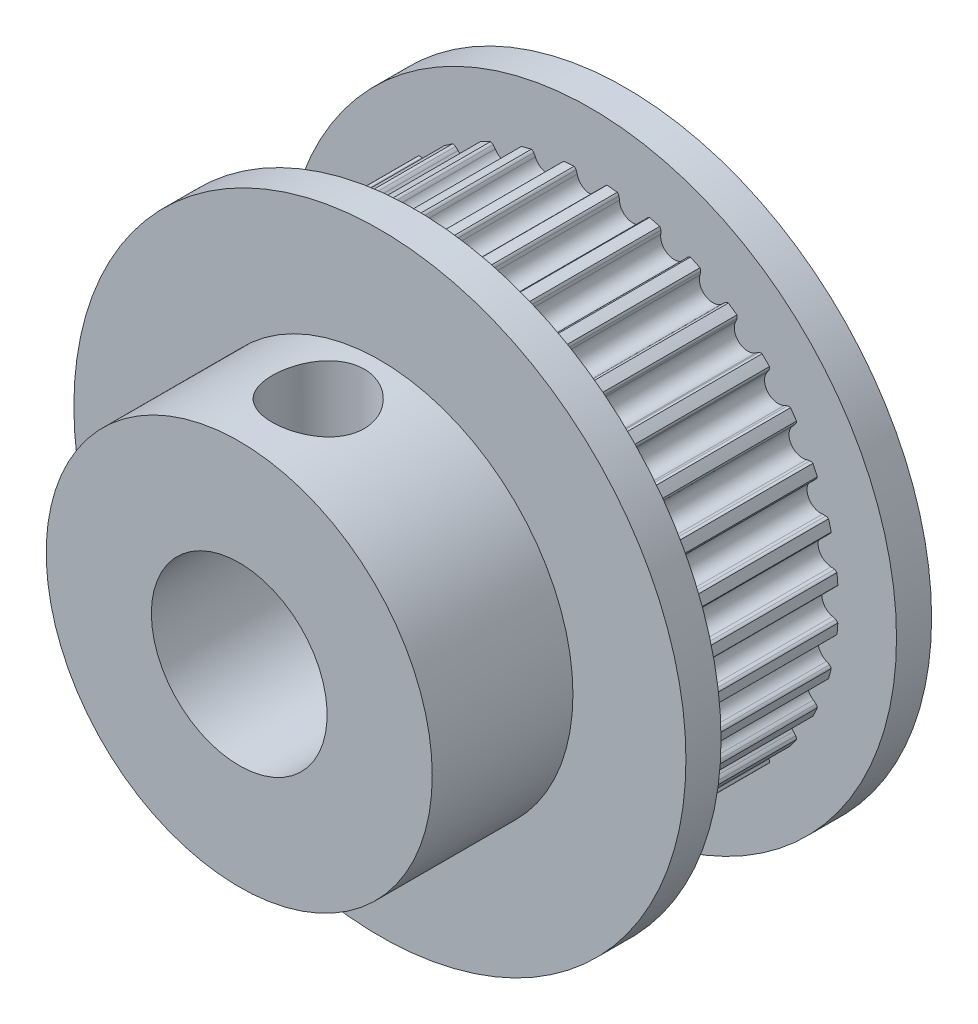
SolidWorks part; units mm, degrees
ref_plane "Front Plane" through (0, 0, 0) normal (0, 0, 1) x (1, 0, 0)
ref_plane "Top Plane" through (0, 0, 0) normal (0, 1, 0) x (1, 0, 0)
ref_plane "Right Plane" through (0, 0, 0) normal (1, 0, 0) x (0, 0, -1)
sketch "Sketch1" plane through (0, 0, 0) normal (0, 1, 0) x (1, 0, 0)
  line L0 (13.843, -3.9687) -> (0, -3.9687)
  line L1 (0, -3.9687) -> (0, -5.5562)
  line L2 (0, -5.5562) -> (13.843, -5.5562)
  line L3 (13.843, -5.5562) -> (13.843, -3.9687)
  line L4 (0, -3.9687) -> (0, -5.5562) construction
revolve "Revolve1" add sketch "Sketch1" angle 360 about L4 reverse direction yes
sketch "Sketch2" plane through (0, 0, 3.9687) normal (0, 0, -1) x (-1, 0, 0)
  arc A0 (-3.1309, 10.7682) -> (-2.6727, 10.891) centre (0, 0) cw
  arc A6 (-1.2134, 11.1483) -> (-0.7409, 11.1896) centre (0, 0) cw
  arc A7 (-4.5233, 10.2614) -> (-4.4045, 10.2) centre (-4.5654, 10.0341) cw
  arc A8 (-4.4045, 10.2) -> (-4.3083, 10.0819) centre (-4.8573, 9.7334) cw
  arc A9 (-4.3083, 10.0819) -> (-3.1801, 10.4925) centre (-3.7894, 10.4113) ccw
  arc A10 (-3.1801, 10.4925) -> (-3.1824, 10.6448) centre (-2.5356, 10.5784) cw
  arc A11 (-3.1824, 10.6448) -> (-3.1309, 10.7682) centre (-2.9525, 10.6212) cw
  arc A12 (-2.6727, 10.891) -> (-2.5663, 10.8099) centre (-2.7537, 10.6745) cw
  arc A13 (-2.5663, 10.8099) -> (-2.4922, 10.6768) centre (-3.0933, 10.429) cw
  arc A14 (-2.4922, 10.6768) -> (-1.3098, 10.8853) centre (-1.9239, 10.9112) ccw
  arc A15 (-1.3098, 10.8853) -> (-1.2856, 11.0357) centre (-0.6601, 10.858) cw
  arc A16 (-1.2856, 11.0357) -> (-1.2134, 11.1483) centre (-1.0633, 10.9725) cw
  arc A17 (-0.7409, 11.1896) -> (-0.6502, 11.0913) centre (-0.8582, 10.9905) cw
  arc A18 (-0.6502, 11.0913) -> (-0.6003, 10.9474) centre (-1.2354, 10.8077) cw
  arc A19 (-0.6003, 10.9474) -> (0.6003, 10.9474) centre (0, 11.0795) ccw
  arc A20 (0.6003, 10.9474) -> (0.6502, 11.0913) centre (1.2354, 10.8077) cw
  arc A21 (0.6502, 11.0913) -> (0.7409, 11.1896) centre (0.8582, 10.9905) cw
  arc A22 (1.2134, 11.1483) -> (1.2856, 11.0357) centre (1.0633, 10.9725) cw
  arc A23 (1.2856, 11.0357) -> (1.3098, 10.8853) centre (0.6601, 10.858) cw
  arc A24 (1.3098, 10.8853) -> (2.4922, 10.6768) centre (1.9239, 10.9112) ccw
  arc A25 (2.4922, 10.6768) -> (2.5663, 10.8099) centre (3.0933, 10.429) cw
  arc A26 (2.5663, 10.8099) -> (2.6727, 10.891) centre (2.7537, 10.6745) cw
  arc A27 (3.1309, 10.7682) -> (3.1824, 10.6448) centre (2.9525, 10.6212) cw
  arc A28 (3.1824, 10.6448) -> (3.1801, 10.4925) centre (2.5356, 10.5784) cw
  arc A29 (3.1801, 10.4925) -> (4.3083, 10.0819) centre (3.7894, 10.4113) ccw
  arc A30 (4.3083, 10.0819) -> (4.4045, 10.2) centre (4.8573, 9.7334) cw
  arc A31 (4.4045, 10.2) -> (4.5233, 10.2614) centre (4.5654, 10.0341) cw
  arc A32 (4.9532, 10.0609) -> (4.9825, 9.9305) centre (4.752, 9.9471) cw
  arc A33 (4.9825, 9.9305) -> (4.9538, 9.7809) centre (4.334, 9.9774) cw
  arc A34 (4.9538, 9.7809) -> (5.9936, 9.1806) centre (5.5397, 9.5951) ccw
  arc A35 (5.9936, 9.1806) -> (6.1088, 9.2802) centre (6.4737, 8.742) cw
  arc A36 (6.1088, 9.2802) -> (6.2364, 9.32) centre (6.2385, 9.0889) cw
  arc A37 (6.625, 9.048) -> (6.6312, 8.9144) centre (6.4071, 8.9709) cw
  arc A38 (6.6312, 8.9144) -> (6.577, 8.7721) centre (6.0007, 9.0732) cw
  arc A39 (6.577, 8.7721) -> (7.4967, 8.0003) centre (7.1218, 8.4874) ccw
  arc A40 (7.4967, 8.0003) -> (7.6275, 8.0784) centre (7.8934, 7.4851) cw
  arc A41 (7.6275, 8.0784) -> (7.7601, 8.0955) centre (7.722, 7.8675) cw
  arc A42 (8.0955, 7.7601) -> (8.0784, 7.6275) centre (7.8675, 7.722) cw
  arc A43 (8.0784, 7.6275) -> (8.0003, 7.4967) centre (7.4851, 7.8934) cw
  arc A44 (8.0003, 7.4967) -> (8.7721, 6.577) centre (8.4874, 7.1218) ccw
  arc A45 (8.7721, 6.577) -> (8.9144, 6.6312) centre (9.0732, 6.0007) cw
  arc A46 (8.9144, 6.6312) -> (9.048, 6.625) centre (8.9709, 6.4071) cw
  arc A47 (9.32, 6.2364) -> (9.2802, 6.1088) centre (9.0889, 6.2385) cw
  arc A48 (9.2802, 6.1088) -> (9.1806, 5.9936) centre (8.742, 6.4737) cw
  arc A49 (9.1806, 5.9936) -> (9.7809, 4.9538) centre (9.5951, 5.5397) ccw
  arc A50 (9.7809, 4.9538) -> (9.9305, 4.9825) centre (9.9774, 4.334) cw
  arc A51 (9.9305, 4.9825) -> (10.0609, 4.9532) centre (9.9471, 4.752) cw
  arc A52 (10.2614, 4.5233) -> (10.2, 4.4045) centre (10.0341, 4.5654) cw
  arc A53 (10.2, 4.4045) -> (10.0819, 4.3083) centre (9.7334, 4.8573) cw
  arc A54 (10.0819, 4.3083) -> (10.4925, 3.1801) centre (10.4113, 3.7894) ccw
  arc A55 (10.4925, 3.1801) -> (10.6448, 3.1824) centre (10.5784, 2.5356) cw
  arc A56 (10.6448, 3.1824) -> (10.7682, 3.1309) centre (10.6212, 2.9525) cw
  arc A57 (10.891, 2.6727) -> (10.8099, 2.5663) centre (10.6745, 2.7537) cw
  arc A58 (10.8099, 2.5663) -> (10.6768, 2.4922) centre (10.429, 3.0933) cw
  arc A59 (10.6768, 2.4922) -> (10.8853, 1.3098) centre (10.9112, 1.9239) ccw
  arc A60 (10.8853, 1.3098) -> (11.0357, 1.2856) centre (10.858, 0.6601) cw
  arc A61 (11.0357, 1.2856) -> (11.1483, 1.2134) centre (10.9725, 1.0633) cw
  arc A62 (11.1896, 0.7409) -> (11.0913, 0.6502) centre (10.9905, 0.8582) cw
  arc A63 (11.0913, 0.6502) -> (10.9474, 0.6003) centre (10.8077, 1.2354) cw
  arc A64 (10.9474, 0.6003) -> (10.9474, -0.6003) centre (11.0795, 0) ccw
  arc A65 (10.9474, -0.6003) -> (11.0913, -0.6502) centre (10.8077, -1.2354) cw
  arc A66 (11.0913, -0.6502) -> (11.1896, -0.7409) centre (10.9905, -0.8582) cw
  arc A67 (11.1483, -1.2134) -> (11.0357, -1.2856) centre (10.9725, -1.0633) cw
  arc A68 (11.0357, -1.2856) -> (10.8853, -1.3098) centre (10.858, -0.6601) cw
  arc A69 (10.8853, -1.3098) -> (10.6768, -2.4922) centre (10.9112, -1.9239) ccw
  arc A70 (10.6768, -2.4922) -> (10.8099, -2.5663) centre (10.429, -3.0933) cw
  arc A71 (10.8099, -2.5663) -> (10.891, -2.6727) centre (10.6745, -2.7537) cw
  arc A72 (10.7682, -3.1309) -> (10.6448, -3.1824) centre (10.6212, -2.9525) cw
  arc A73 (10.6448, -3.1824) -> (10.4925, -3.1801) centre (10.5784, -2.5356) cw
  arc A74 (10.4925, -3.1801) -> (10.0819, -4.3083) centre (10.4113, -3.7894) ccw
  arc A75 (10.0819, -4.3083) -> (10.2, -4.4045) centre (9.7334, -4.8573) cw
  arc A76 (10.2, -4.4045) -> (10.2614, -4.5233) centre (10.0341, -4.5654) cw
  arc A77 (10.0609, -4.9532) -> (9.9305, -4.9825) centre (9.9471, -4.752) cw
  arc A78 (9.9305, -4.9825) -> (9.7809, -4.9538) centre (9.9774, -4.334) cw
  arc A79 (9.7809, -4.9538) -> (9.1806, -5.9936) centre (9.5951, -5.5397) ccw
  arc A80 (9.1806, -5.9936) -> (9.2802, -6.1088) centre (8.742, -6.4737) cw
  arc A81 (9.2802, -6.1088) -> (9.32, -6.2364) centre (9.0889, -6.2385) cw
  arc A82 (9.048, -6.625) -> (8.9144, -6.6312) centre (8.9709, -6.4071) cw
  arc A83 (8.9144, -6.6312) -> (8.7721, -6.577) centre (9.0732, -6.0007) cw
  arc A84 (8.7721, -6.577) -> (8.0003, -7.4967) centre (8.4874, -7.1218) ccw
  arc A85 (8.0003, -7.4967) -> (8.0784, -7.6275) centre (7.4851, -7.8934) cw
  arc A86 (8.0784, -7.6275) -> (8.0955, -7.7601) centre (7.8675, -7.722) cw
  arc A87 (7.7601, -8.0955) -> (7.6275, -8.0784) centre (7.722, -7.8675) cw
  arc A88 (7.6275, -8.0784) -> (7.4967, -8.0003) centre (7.8934, -7.4851) cw
  arc A89 (7.4967, -8.0003) -> (6.577, -8.7721) centre (7.1218, -8.4874) ccw
  arc A90 (6.577, -8.7721) -> (6.6312, -8.9144) centre (6.0007, -9.0732) cw
  arc A91 (6.6312, -8.9144) -> (6.625, -9.048) centre (6.4071, -8.9709) cw
  arc A92 (6.2364, -9.32) -> (6.1088, -9.2802) centre (6.2385, -9.0889) cw
  arc A93 (6.1088, -9.2802) -> (5.9936, -9.1806) centre (6.4737, -8.742) cw
  arc A94 (5.9936, -9.1806) -> (4.9538, -9.7809) centre (5.5397, -9.5951) ccw
  arc A95 (4.9538, -9.7809) -> (4.9825, -9.9305) centre (4.334, -9.9774) cw
  arc A96 (4.9825, -9.9305) -> (4.9532, -10.0609) centre (4.752, -9.9471) cw
  arc A97 (4.5233, -10.2614) -> (4.4045, -10.2) centre (4.5654, -10.0341) cw
  arc A98 (4.4045, -10.2) -> (4.3083, -10.0819) centre (4.8573, -9.7334) cw
  arc A99 (4.3083, -10.0819) -> (3.1801, -10.4925) centre (3.7894, -10.4113) ccw
  arc A100 (3.1801, -10.4925) -> (3.1824, -10.6448) centre (2.5356, -10.5784) cw
  arc A101 (3.1824, -10.6448) -> (3.1309, -10.7682) centre (2.9525, -10.6212) cw
  arc A102 (2.6727, -10.891) -> (2.5663, -10.8099) centre (2.7537, -10.6745) cw
  arc A103 (2.5663, -10.8099) -> (2.4922, -10.6768) centre (3.0933, -10.429) cw
  arc A104 (2.4922, -10.6768) -> (1.3098, -10.8853) centre (1.9239, -10.9112) ccw
  arc A105 (1.3098, -10.8853) -> (1.2856, -11.0357) centre (0.6601, -10.858) cw
  arc A106 (1.2856, -11.0357) -> (1.2134, -11.1483) centre (1.0633, -10.9725) cw
  arc A107 (0.7409, -11.1896) -> (0.6502, -11.0913) centre (0.8582, -10.9905) cw
  arc A108 (0.6502, -11.0913) -> (0.6003, -10.9474) centre (1.2354, -10.8077) cw
  arc A109 (0.6003, -10.9474) -> (-0.6003, -10.9474) centre (0, -11.0795) ccw
  arc A110 (-0.6003, -10.9474) -> (-0.6502, -11.0913) centre (-1.2354, -10.8077) cw
  arc A111 (-0.6502, -11.0913) -> (-0.7409, -11.1896) centre (-0.8582, -10.9905) cw
  arc A112 (-1.2134, -11.1483) -> (-1.2856, -11.0357) centre (-1.0633, -10.9725) cw
  arc A113 (-1.2856, -11.0357) -> (-1.3098, -10.8853) centre (-0.6601, -10.858) cw
  arc A114 (-1.3098, -10.8853) -> (-2.4922, -10.6768) centre (-1.9239, -10.9112) ccw
  arc A115 (-2.4922, -10.6768) -> (-2.5663, -10.8099) centre (-3.0933, -10.429) cw
  arc A116 (-2.5663, -10.8099) -> (-2.6727, -10.891) centre (-2.7537, -10.6745) cw
  arc A117 (-3.1309, -10.7682) -> (-3.1824, -10.6448) centre (-2.9525, -10.6212) cw
  arc A118 (-3.1824, -10.6448) -> (-3.1801, -10.4925) centre (-2.5356, -10.5784) cw
  arc A119 (-3.1801, -10.4925) -> (-4.3083, -10.0819) centre (-3.7894, -10.4113) ccw
  arc A120 (-4.3083, -10.0819) -> (-4.4045, -10.2) centre (-4.8573, -9.7334) cw
  arc A121 (-4.4045, -10.2) -> (-4.5233, -10.2614) centre (-4.5654, -10.0341) cw
  arc A122 (-4.9532, -10.0609) -> (-4.9825, -9.9305) centre (-4.752, -9.9471) cw
  arc A123 (-4.9825, -9.9305) -> (-4.9538, -9.7809) centre (-4.334, -9.9774) cw
  arc A124 (-4.9538, -9.7809) -> (-5.9936, -9.1806) centre (-5.5397, -9.5951) ccw
  arc A125 (-5.9936, -9.1806) -> (-6.1088, -9.2802) centre (-6.4737, -8.742) cw
  arc A126 (-6.1088, -9.2802) -> (-6.2364, -9.32) centre (-6.2385, -9.0889) cw
  arc A127 (-6.625, -9.048) -> (-6.6312, -8.9144) centre (-6.4071, -8.9709) cw
  arc A128 (-6.6312, -8.9144) -> (-6.577, -8.7721) centre (-6.0007, -9.0732) cw
  arc A129 (-6.577, -8.7721) -> (-7.4967, -8.0003) centre (-7.1218, -8.4874) ccw
  arc A130 (-7.4967, -8.0003) -> (-7.6275, -8.0784) centre (-7.8934, -7.4851) cw
  arc A131 (-7.6275, -8.0784) -> (-7.7601, -8.0955) centre (-7.722, -7.8675) cw
  arc A132 (-8.0955, -7.7601) -> (-8.0784, -7.6275) centre (-7.8675, -7.722) cw
  arc A133 (-8.0784, -7.6275) -> (-8.0003, -7.4967) centre (-7.4851, -7.8934) cw
  arc A134 (-8.0003, -7.4967) -> (-8.7721, -6.577) centre (-8.4874, -7.1218) ccw
  arc A135 (-8.7721, -6.577) -> (-8.9144, -6.6312) centre (-9.0732, -6.0007) cw
  arc A136 (-8.9144, -6.6312) -> (-9.048, -6.625) centre (-8.9709, -6.4071) cw
  arc A137 (-9.32, -6.2364) -> (-9.2802, -6.1088) centre (-9.0889, -6.2385) cw
  arc A138 (-9.2802, -6.1088) -> (-9.1806, -5.9936) centre (-8.742, -6.4737) cw
  arc A139 (-9.1806, -5.9936) -> (-9.7809, -4.9538) centre (-9.5951, -5.5397) ccw
  arc A140 (-9.7809, -4.9538) -> (-9.9305, -4.9825) centre (-9.9774, -4.334) cw
  arc A141 (-9.9305, -4.9825) -> (-10.0609, -4.9532) centre (-9.9471, -4.752) cw
  arc A142 (-10.2614, -4.5233) -> (-10.2, -4.4045) centre (-10.0341, -4.5654) cw
  arc A143 (-10.2, -4.4045) -> (-10.0819, -4.3083) centre (-9.7334, -4.8573) cw
  arc A144 (-10.0819, -4.3083) -> (-10.4925, -3.1801) centre (-10.4113, -3.7894) ccw
  arc A145 (-10.4925, -3.1801) -> (-10.6448, -3.1824) centre (-10.5784, -2.5356) cw
  arc A146 (-10.6448, -3.1824) -> (-10.7682, -3.1309) centre (-10.6212, -2.9525) cw
  arc A147 (-10.891, -2.6727) -> (-10.8099, -2.5663) centre (-10.6745, -2.7537) cw
  arc A148 (-10.8099, -2.5663) -> (-10.6768, -2.4922) centre (-10.429, -3.0933) cw
  arc A149 (-10.6768, -2.4922) -> (-10.8853, -1.3098) centre (-10.9112, -1.9239) ccw
  arc A150 (-10.8853, -1.3098) -> (-11.0357, -1.2856) centre (-10.858, -0.6601) cw
  arc A151 (-11.0357, -1.2856) -> (-11.1483, -1.2134) centre (-10.9725, -1.0633) cw
  arc A152 (-11.1896, -0.7409) -> (-11.0913, -0.6502) centre (-10.9905, -0.8582) cw
  arc A153 (-11.0913, -0.6502) -> (-10.9474, -0.6003) centre (-10.8077, -1.2354) cw
  arc A154 (-10.9474, -0.6003) -> (-10.9474, 0.6003) centre (-11.0795, 0) ccw
  arc A155 (-10.9474, 0.6003) -> (-11.0913, 0.6502) centre (-10.8077, 1.2354) cw
  arc A156 (-11.0913, 0.6502) -> (-11.1896, 0.7409) centre (-10.9905, 0.8582) cw
  arc A157 (-11.1483, 1.2134) -> (-11.0357, 1.2856) centre (-10.9725, 1.0633) cw
  arc A158 (-11.0357, 1.2856) -> (-10.8853, 1.3098) centre (-10.858, 0.6601) cw
  arc A159 (-10.8853, 1.3098) -> (-10.6768, 2.4922) centre (-10.9112, 1.9239) ccw
  arc A160 (-10.6768, 2.4922) -> (-10.8099, 2.5663) centre (-10.429, 3.0933) cw
  arc A161 (-10.8099, 2.5663) -> (-10.891, 2.6727) centre (-10.6745, 2.7537) cw
  arc A162 (-10.7682, 3.1309) -> (-10.6448, 3.1824) centre (-10.6212, 2.9525) cw
  arc A163 (-10.6448, 3.1824) -> (-10.4925, 3.1801) centre (-10.5784, 2.5356) cw
  arc A164 (-10.4925, 3.1801) -> (-10.0819, 4.3083) centre (-10.4113, 3.7894) ccw
  arc A165 (-10.0819, 4.3083) -> (-10.2, 4.4045) centre (-9.7334, 4.8573) cw
  arc A166 (-10.2, 4.4045) -> (-10.2614, 4.5233) centre (-10.0341, 4.5654) cw
  arc A167 (-10.0609, 4.9532) -> (-9.9305, 4.9825) centre (-9.9471, 4.752) cw
  arc A168 (-9.9305, 4.9825) -> (-9.7809, 4.9538) centre (-9.9774, 4.334) cw
  arc A169 (-9.7809, 4.9538) -> (-9.1806, 5.9936) centre (-9.5951, 5.5397) ccw
  arc A170 (-9.1806, 5.9936) -> (-9.2802, 6.1088) centre (-8.742, 6.4737) cw
  arc A171 (-9.2802, 6.1088) -> (-9.32, 6.2364) centre (-9.0889, 6.2385) cw
  arc A172 (-9.048, 6.625) -> (-8.9144, 6.6312) centre (-8.9709, 6.4071) cw
  arc A173 (-8.9144, 6.6312) -> (-8.7721, 6.577) centre (-9.0732, 6.0007) cw
  arc A174 (-8.7721, 6.577) -> (-8.0003, 7.4967) centre (-8.4874, 7.1218) ccw
  arc A175 (-8.0003, 7.4967) -> (-8.0784, 7.6275) centre (-7.4851, 7.8934) cw
  arc A176 (-8.0784, 7.6275) -> (-8.0955, 7.7601) centre (-7.8675, 7.722) cw
  arc A177 (-7.7601, 8.0955) -> (-7.6275, 8.0784) centre (-7.722, 7.8675) cw
  arc A178 (-7.6275, 8.0784) -> (-7.4967, 8.0003) centre (-7.8934, 7.4851) cw
  arc A179 (-7.4967, 8.0003) -> (-6.577, 8.7721) centre (-7.1218, 8.4874) ccw
  arc A180 (-6.577, 8.7721) -> (-6.6312, 8.9144) centre (-6.0007, 9.0732) cw
  arc A181 (-6.6312, 8.9144) -> (-6.625, 9.048) centre (-6.4071, 8.9709) cw
  arc A182 (-6.2364, 9.32) -> (-6.1088, 9.2802) centre (-6.2385, 9.0889) cw
  arc A183 (-6.1088, 9.2802) -> (-5.9936, 9.1806) centre (-6.4737, 8.742) cw
  arc A184 (-5.9936, 9.1806) -> (-4.9538, 9.7809) centre (-5.5397, 9.5951) ccw
  arc A185 (-4.9538, 9.7809) -> (-4.9825, 9.9305) centre (-4.334, 9.9774) cw
  arc A186 (-4.9825, 9.9305) -> (-4.9532, 10.0609) centre (-4.752, 9.9471) cw
  arc A187 (0.7409, 11.1896) -> (1.2134, 11.1483) centre (0, 0) cw
  arc A188 (2.6727, 10.891) -> (3.1309, 10.7682) centre (0, 0) cw
  arc A189 (4.5233, 10.2614) -> (4.9532, 10.0609) centre (0, 0) cw
  arc A190 (6.2364, 9.32) -> (6.625, 9.048) centre (0, 0) cw
  arc A191 (7.7601, 8.0955) -> (8.0955, 7.7601) centre (0, 0) cw
  arc A192 (9.048, 6.625) -> (9.32, 6.2364) centre (0, 0) cw
  arc A193 (10.0609, 4.9532) -> (10.2614, 4.5233) centre (0, 0) cw
  arc A194 (10.7682, 3.1309) -> (10.891, 2.6727) centre (0, 0) cw
  arc A195 (11.1483, 1.2134) -> (11.1896, 0.7409) centre (0, 0) cw
  arc A196 (11.1896, -0.7409) -> (11.1483, -1.2134) centre (0, 0) cw
  arc A197 (10.891, -2.6727) -> (10.7682, -3.1309) centre (0, 0) cw
  arc A198 (10.2614, -4.5233) -> (10.0609, -4.9532) centre (0, 0) cw
  arc A199 (9.32, -6.2364) -> (9.048, -6.625) centre (0, 0) cw
  arc A200 (8.0955, -7.7601) -> (7.7601, -8.0955) centre (0, 0) cw
  arc A201 (6.625, -9.048) -> (6.2364, -9.32) centre (0, 0) cw
  arc A202 (4.9532, -10.0609) -> (4.5233, -10.2614) centre (0, 0) cw
  arc A203 (3.1309, -10.7682) -> (2.6727, -10.891) centre (0, 0) cw
  arc A204 (1.2134, -11.1483) -> (0.7409, -11.1896) centre (0, 0) cw
  arc A205 (-0.7409, -11.1896) -> (-1.2134, -11.1483) centre (0, 0) cw
  arc A206 (-2.6727, -10.891) -> (-3.1309, -10.7682) centre (0, 0) cw
  arc A207 (-4.5233, -10.2614) -> (-4.9532, -10.0609) centre (0, 0) cw
  arc A208 (-6.2364, -9.32) -> (-6.625, -9.048) centre (0, 0) cw
  arc A209 (-7.7601, -8.0955) -> (-8.0955, -7.7601) centre (0, 0) cw
  arc A210 (-9.048, -6.625) -> (-9.32, -6.2364) centre (0, 0) cw
  arc A211 (-10.0609, -4.9532) -> (-10.2614, -4.5233) centre (0, 0) cw
  arc A212 (-10.7682, -3.1309) -> (-10.891, -2.6727) centre (0, 0) cw
  arc A213 (-11.1483, -1.2134) -> (-11.1896, -0.7409) centre (0, 0) cw
  arc A214 (-11.1896, 0.7409) -> (-11.1483, 1.2134) centre (0, 0) cw
  arc A215 (-10.891, 2.6727) -> (-10.7682, 3.1309) centre (0, 0) cw
  arc A216 (-10.2614, 4.5233) -> (-10.0609, 4.9532) centre (0, 0) cw
  arc A217 (-9.32, 6.2364) -> (-9.048, 6.625) centre (0, 0) cw
  arc A218 (-8.0955, 7.7601) -> (-7.7601, 8.0955) centre (0, 0) cw
  arc A219 (-6.625, 9.048) -> (-6.2364, 9.32) centre (0, 0) cw
  arc A220 (-4.9532, 10.0609) -> (-4.5233, 10.2614) centre (0, 0) cw
  point P410 (0, 0)
  dimension "D1" = 36
extrude "Boss-Extrude1" add sketch "Sketch2" along normal blind 7.9375
ref_plane "Plane1" through (0, 0, -3.9688) normal (0, 0, 1) x (1, 0, 0)
sketch "Sketch3" plane through (0, 0, -3.9688) normal (0, 0, 1) x (1, 0, 0)
  circle A0 centre (0, 0) radius 13.843
extrude "Boss-Extrude2" add sketch "Sketch3" against normal blind 1.5875
sketch "Sketch4" plane through (0, 0, 5.5562) normal (0, 0, 1) x (1, 0, 0)
  circle A0 centre (0, 0) radius 8.7312
extrude "Boss-Extrude3" add sketch "Sketch4" along normal blind 6.3627
hole_wizard "M7 Clearance Hole1" positions "Sketch6" profile "Sketch5" hole size "M7" standard "ANSI Metric"
sketch "Sketch6" plane through (0, 0, -5.5562) normal (0, 0, -1) x (-1, 0, 0)
  point P0 (0, 0)
sketch "Sketch5" plane through (0, 0, -5.5562) normal (1, 0, 0) x (0, 1, 0)
  line L0 (0, 0) -> (0, 17.4752)
  line L1 (0, 17.4752) -> (3.9751, 17.4752)
  line L2 (3.9751, 17.4752) -> (3.9751, 0)
  line L5 (3.9751, 0) -> (0, 0)
  line L11 (0, -6.35) -> (0, 107.95) construction
  dimension "Thru Hole Dia." = 7.9502
  dimension "Thru Hole Depth" = 17.4752
ref_plane "Plane2" through (0, 3.3858, 0) normal (0, -1, 0) x (-1, 0, 0)
hole_wizard "M3.5 Clearance Hole1" positions "Sketch8" profile "Sketch7" hole size "M3.5" standard "ANSI Metric"
sketch "Sketch8" plane through (0, 3.3858, 0) normal (0, -1, 0) x (-1, 0, 0)
  point P0 (0, -8.3471)
sketch "Sketch7" plane through (0, 3.3858, 8.3471) normal (1, 0, 0) x (0, 0, -1)
  line L0 (0, 0) -> (0, 10.4572)
  line L1 (0, 10.4572) -> (2.0828, 10.4572)
  line L2 (2.0828, 10.4572) -> (2.0828, 0)
  line L5 (2.0828, 0) -> (0, 0)
  line L11 (0, -6.35) -> (0, 107.95) construction
  dimension "Thru Hole Dia." = 4.1656
  dimension "Thru Hole Depth" = 10.4572
